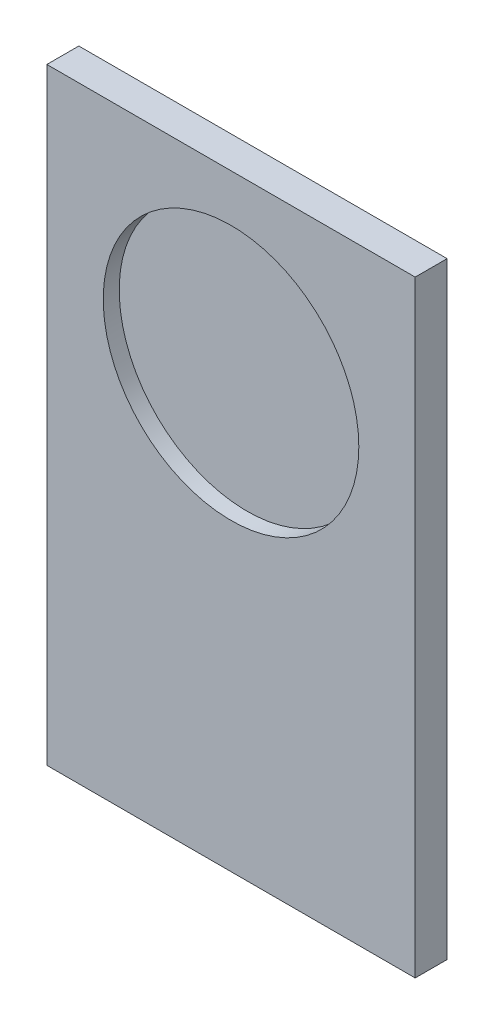
SolidWorks part; units mm, degrees
ref_plane "정면" through (0, 0, 0) normal (0, 0, 1) x (1, 0, 0)
ref_plane "윗면" through (0, 0, 0) normal (0, 1, 0) x (1, 0, 0)
ref_plane "우측면" through (0, 0, 0) normal (1, 0, 0) x (0, 0, -1)
sketch "스케치1" plane through (0, 0, 0) normal (0, 0, 1) x (1, 0, 0)
  line L1 (-28.82, 62.5) -> (28.82, 62.5)
  line L2 (-28.82, 62.5) -> (-28.82, -62.5)
  line L3 (-28.82, -62.5) -> (28.82, -62.5)
  line L4 (28.82, 62.5) -> (28.82, -62.5)
  line L5 (-28.82, 62.5) -> (28.82, -62.5) construction
  line L6 (-28.82, -62.5) -> (28.82, 62.5) construction
  point P0 (0, 0)
  dimension "D1" = 57.64
  dimension "D2" = 125
extrude "보스-돌출1" add sketch "스케치1" along normal blind 5
sketch "스케치2" plane through (0, 0, 5) normal (0, 0, 1) x (1, 0, 0)
  arc A19 (20, 5.1017) -> (-20, 5.1017) centre (0, 5.1017) cw
  arc A20 (-20, 5.1017) -> (20, 5.1017) centre (0, 5.1017) cw
  dimension "D1" = 20
extrude "컷-돌출1" cut sketch "스케치2" against normal blind 2.5 contours A20 A19
sketch "스케치3" plane through (0, 0, 5) normal (0, 0, 1) x (1, 0, 0)
  line L1 (-28.82, 62.5) -> (28.82, 62.5)
  line L2 (-28.82, 62.5) -> (-28.82, 32.5)
  line L3 (-28.82, 32.5) -> (28.82, 32.5)
  line L4 (28.82, 62.5) -> (28.82, 32.5)
  dimension "D1" = 30
extrude "컷-돌출2" cut sketch "스케치3" against normal blind 10
